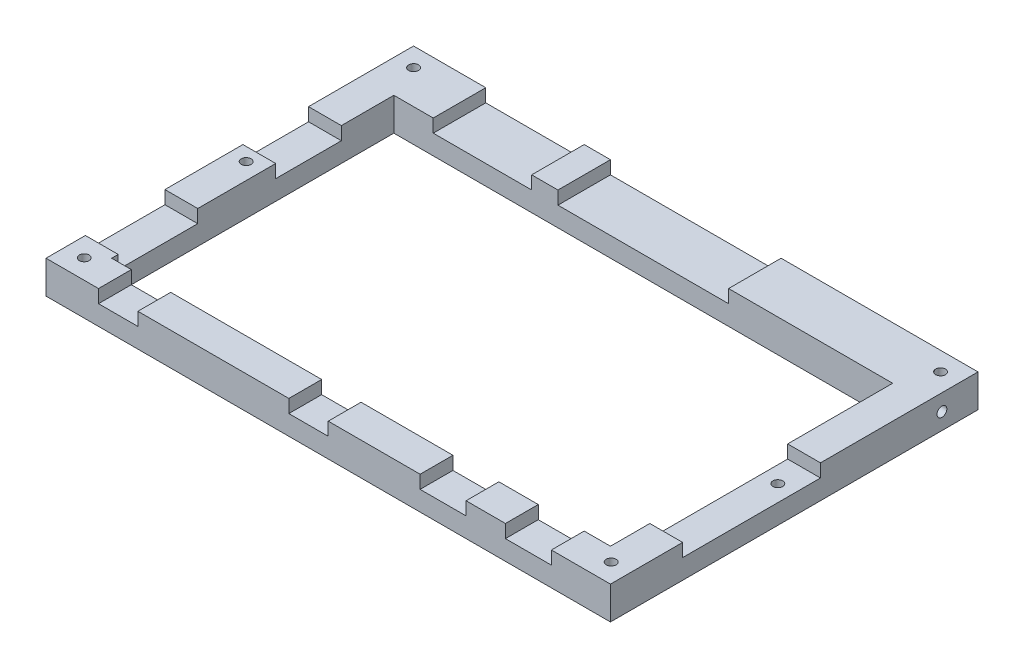
SolidWorks part; units mm, degrees
ref_plane "前视基准面" through (0, 0, 0) normal (0, 0, 1) x (1, 0, 0)
ref_plane "上视基准面" through (0, 0, 0) normal (0, 1, 0) x (1, 0, 0)
ref_plane "右视基准面" through (0, 0, 0) normal (1, 0, 0) x (0, 0, -1)
other "Configuration Table"
sketch "草图1" plane through (0, 0, 0) normal (0, 1, 0) x (1, 0, 0)
  line L1 (-43, -60.5) -> (43, -60.5)
  line L2 (-43, -60.5) -> (-43, 60.5)
  line L3 (-43, 60.5) -> (43, 60.5)
  line L4 (43, -60.5) -> (43, 60.5)
  line L5 (-43, -60.5) -> (43, 60.5) construction
  line L6 (-43, 60.5) -> (43, -60.5) construction
  line L7 (-25, 50.5) -> (25, 50.5)
  line L8 (-25, 50.5) -> (-25, -4.5)
  line L9 (-25, -4.5) -> (25, -4.5)
  line L10 (25, 50.5) -> (25, -4.5)
  line L11 (-25, -25.5) -> (25, -25.5)
  line L12 (-25, -25.5) -> (-25, -50.5)
  line L13 (-25, -50.5) -> (25, -50.5)
  line L14 (25, -25.5) -> (25, -50.5)
  line L15 (-43, -60.5) -> (43, -60.5)
  line L16 (-43, -60.5) -> (-43, -113.5)
  line L17 (-43, -113.5) -> (43, -113.5)
  line L18 (43, -60.5) -> (43, -113.5)
  line L19 (-38, -65.5) -> (38, -65.5)
  line L20 (-38, -65.5) -> (-38, -108.5)
  line L21 (-38, -108.5) -> (38, -108.5)
  line L22 (38, -65.5) -> (38, -108.5)
  point P0 (0, 0)
  dimension "D1" = 86
  dimension "D2" = 121
  dimension "D3" = 10
  dimension "D4" = 18
  dimension "D5" = 18
  dimension "D6" = 55
  dimension "D7" = 10
  dimension "D8" = 25
  dimension "D9" = 5
  dimension "D10" = 5
  dimension "D11" = 5
  dimension "D12" = 5
  dimension "D13" = 53
extrude "凸台-拉伸1" add sketch "草图1" along normal blind 5 contours L18 L1 L16 L17 L19 L22 L21 L20 | L2 L3 L4 L1 | L9 L10 L7 L8 | L11 L14 L13 L12 region at (0, 0, 61.5102)
sketch "草图4" plane through (0, 5, 0) normal (0, 1, 0) x (1, 0, 0)
  line L0 (-43, 60.5) -> (43, 60.5) construction
  line L1 (-34.35, 57.5) -> (34.35, 57.5)
  line L2 (-34.35, 57.5) -> (-34.35, -57.5)
  line L3 (-34.35, -57.5) -> (34.35, -57.5)
  line L4 (34.35, 57.5) -> (34.35, -57.5)
  line L5 (-32.35, -18.5) -> (32.35, -18.5)
  line L6 (-32.35, -18.5) -> (-32.35, -55.5)
  line L7 (-32.35, -55.5) -> (32.35, -55.5)
  line L8 (32.35, -18.5) -> (32.35, -55.5)
  line L9 (32.35, -14.5) -> (-32.35, -14.5)
  line L10 (32.35, -14.5) -> (32.35, 55.5)
  line L11 (32.35, 55.5) -> (-32.35, 55.5)
  line L12 (-32.35, -14.5) -> (-32.35, 55.5)
  line L13 (43, 60.5) -> (43, -113.5) construction
  line L14 (-43, 60.5) -> (-43, -113.5) construction
  dimension "D1" = 5
  dimension "D2" = 10.65
  dimension "D3" = 10.65
  dimension "D4" = 2
  dimension "D5" = 2
  dimension "D6" = 2
  dimension "D7" = 70
  dimension "D8" = 79
  dimension "D9" = 37
  dimension "D10" = 2
extrude "凸台-拉伸2" add sketch "草图4" along normal blind 10 contours L3 L4 L1 L2 | L6 L7 L8 L5 | L12 L11 L10 L9
sketch "草图5" plane through (0, 5, 0) normal (0, 1, 0) x (1, 0, 0)
  line L0 (-43, 60.5) -> (-43, -113.5) construction
  line L1 (43, 60.5) -> (43, -113.5) construction
  line L2 (-43, 60.5) -> (43, 60.5) construction
  line L3 (-43, -85.5) -> (-38, -85.5)
  line L4 (-38, -65.5) -> (-38, -108.5) construction
  line L5 (-23.6333, -57.5) -> (-23.6333, -113.5)
  line L6 (-34.35, -57.5) -> (34.35, -57.5) construction
  line L7 (-43, -113.5) -> (43, -113.5) construction
  line L8 (38, -85.5) -> (43, -85.5)
  line L9 (38, -65.5) -> (38, -108.5) construction
  line L10 (-25, -25.5) -> (-25, -50.5) construction
  line L12 (-34.35, 57.5) -> (34.35, 57.5) construction
  line L13 (-25, -4.5) -> (25, -4.5) construction
  circle A0 centre (-39, 20.5) radius 0.75
  circle A1 centre (39, 20.5) radius 0.75
  circle A2 centre (-39, -32.5) radius 0.75
  circle A3 centre (39, -32.5) radius 0.75
  circle A4 centre (-40.1428, -60.35) radius 0.75
  circle A5 centre (40.1428, -60.35) radius 0.75
  circle A6 centre (-40.1428, -110.5303) radius 0.75
  circle A7 centre (40.1428, -110.5303) radius 0.75
  circle A8 centre (-40.5, 57.5) radius 0.75
  circle A9 centre (-40.5, -38) radius 0.75
  circle A10 centre (-40.5, -85.5) radius 0.75
  circle A11 centre (40.5, 57.5) radius 0.75
  circle A12 centre (40.5, -38) radius 0.75
  circle A13 centre (40.5, -85.5) radius 0.75
  circle A14 centre (-40.5, -4.5) radius 0.75
  circle A15 centre (40.5, -4.5) radius 0.75
  point P40 (-23.6333, -85.5)
  point P52 (-25, -38)
  dimension "D1" = 1.5
  dimension "D2" = 4
  dimension "D3" = 4
  dimension "D4" = 40
  dimension "D5" = 93
extrude "切除-拉伸1" cut sketch "草图5" against normal through all contours A0 | A2 | A4 | A6 | A7 | A5 | A3 | A1 | A8 | A11 | A9 | A12 | A10 | A13 | A14 | A15
sketch "草图7" plane through (0, 5, 0) normal (0, 1, 0) x (1, 0, 0)
  line L0 (42.9928, -57.5) -> (-42.9928, -57.5) construction
  line L1 (-32, -57.5) -> (-17, -57.5)
  line L2 (-32, -57.5) -> (-32, -65.5)
  line L3 (-32, -65.5) -> (-17, -65.5)
  line L4 (-17, -57.5) -> (-17, -65.5)
  line L5 (-43, 60.5) -> (-43, -113.5) construction
  line L6 (-38, -65.5) -> (38, -65.5) construction
  line L8 (-34.35, -57.5) -> (34.35, -57.5) construction
  line L9 (-13, -57.5) -> (13, -57.5)
  line L10 (-13, -57.5) -> (-13, -65.5)
  line L11 (-13, -65.5) -> (13, -65.5)
  line L12 (13, -57.5) -> (13, -65.5)
  line L13 (-38, -65.5) -> (-38, -108.5) construction
  line L14 (-43, -73.5) -> (-38, -73.5)
  line L15 (-43, -73.5) -> (-43, -83.5)
  line L16 (-43, -83.5) -> (-38, -83.5)
  line L17 (-38, -73.5) -> (-38, -83.5)
  line L18 (-43, -113.5) -> (43, -113.5) construction
  line L19 (-43, -95.3803) -> (-38, -95.3803)
  line L20 (-43, -95.3803) -> (-43, -107.5)
  line L21 (-43, -107.5) -> (-38, -107.5)
  line L22 (-38, -95.3803) -> (-38, -107.5)
  line L23 (-42.9928, -113.3803) -> (42.9928, -113.3803) construction
  line L24 (-38, -108.5) -> (38, -108.5) construction
  line L25 (-35, -108.5) -> (-29, -108.5)
  line L26 (-35, -108.5) -> (-35, -113.5)
  line L27 (-35, -113.5) -> (-29, -113.5)
  line L28 (-29, -108.5) -> (-29, -113.5)
  line L29 (43, 60.5) -> (43, -113.5) construction
  line L30 (-6, -108.5) -> (0, -108.5)
  line L31 (-6, -108.5) -> (-6, -113.5)
  line L32 (-6, -113.5) -> (0, -113.5)
  line L33 (0, -108.5) -> (0, -113.5)
  line L34 (14, -108.5) -> (21, -108.5)
  line L35 (14, -108.5) -> (14, -113.5)
  line L36 (14, -113.5) -> (21, -113.5)
  line L37 (21, -108.5) -> (21, -113.5)
  line L38 (27, -108.5) -> (34, -108.5)
  line L39 (27, -108.5) -> (27, -113.5)
  line L40 (27, -113.5) -> (34, -113.5)
  line L41 (34, -108.5) -> (34, -113.5)
  line L42 (43, -81.5) -> (38, -81.5)
  line L43 (43, -81.5) -> (43, -102.5)
  line L44 (43, -102.5) -> (38, -102.5)
  line L45 (38, -81.5) -> (38, -102.5)
  line L46 (38, -65.5) -> (38, -108.5) construction
  dimension "D1" = 11
  dimension "D2" = 26
  dimension "D3" = 30
  dimension "D4" = 56
  dimension "D5" = 16
  dimension "D6" = 26
  dimension "D7" = 6
  dimension "D8" = 18
  dimension "D9" = 8
  dimension "D10" = 14
  dimension "D11" = 37
  dimension "D12" = 43
  dimension "D13" = 57
  dimension "D14" = 64
  dimension "D15" = 70
  dimension "D16" = 77
  dimension "D17" = 11
  dimension "D18" = 32
extrude "切除-拉伸2" cut sketch "草图7" against normal blind 2
sketch "草图8" plane through (-43, 0, 0) normal (-1, 0, 0) x (0, 0, 1)
  line L0 (0, 0) -> (0, 5)
  line L1 (-57.5, 5) -> (57.5, 5) construction
  circle A0 centre (8, 2.5) radius 0.75
  circle A1 centre (23, 2.5) radius 0.75
  circle A2 centre (52, 2.5) radius 0.75
  circle A3 centre (63, 2.5) radius 0.75
  point P13 (0, 2.5)
  dimension "D1" = 1.5
  dimension "D2" = 8
  dimension "D3" = 15
  dimension "D4" = 29
  dimension "D5" = 11
extrude "切除-拉伸3" cut sketch "草图8" against normal blind 2 contours A0 | A1 | A2 | A3
extrude "切除-拉伸4" cut sketch "草图8<3>" along normal blind 2 from surface contours A0 | A1 | A2 | A3 starting at face at (43, 3.25, 59.25)
sketch "草图8<3>" plane through (-43, 0, 0) normal (-1, 0, 0) x (0, 0, 1) same geometry as "草图8"
sketch "草图9" plane through (0, 0, 0) normal (0, 1, 0) x (1, 0, 0)
  line L0 (0, -14.5) -> (0, -18.5)
  line L1 (-47.378, 69.2613) -> (49.394, 69.2613)
  line L2 (-47.378, 69.2613) -> (-47.378, -16.5)
  line L3 (-47.378, -16.5) -> (49.394, -16.5)
  line L4 (49.394, 69.2613) -> (49.394, -16.5)
  line L5 (49.394, -16.5) -> (-47.378, -16.5)
  line L6 (49.394, -16.5) -> (49.394, -57.5)
  line L7 (49.394, -57.5) -> (-47.378, -57.5)
  line L8 (-47.378, -16.5) -> (-47.378, -57.5)
  line L9 (-47.378, -57.5) -> (55.1903, -57.5)
  line L10 (-47.378, -57.5) -> (-47.378, -123.0227)
  line L11 (-47.378, -123.0227) -> (55.1903, -123.0227)
  line L12 (55.1903, -57.5) -> (55.1903, -123.0227)
  line L13 (32.35, -14.5) -> (-32.35, -14.5) construction
  line L14 (-32.35, -18.5) -> (32.35, -18.5) construction
  line L15 (-34.35, -57.5) -> (34.35, -57.5) construction
  point P15 (0, -16.5)
extrude "切除-拉伸5" cut sketch "草图9" along normal through all contours L4 L1 L2 L3 | L3 L8 L7 L6 region at (1.008, 0, -26.3806) region at (1.008, 0, 37)
